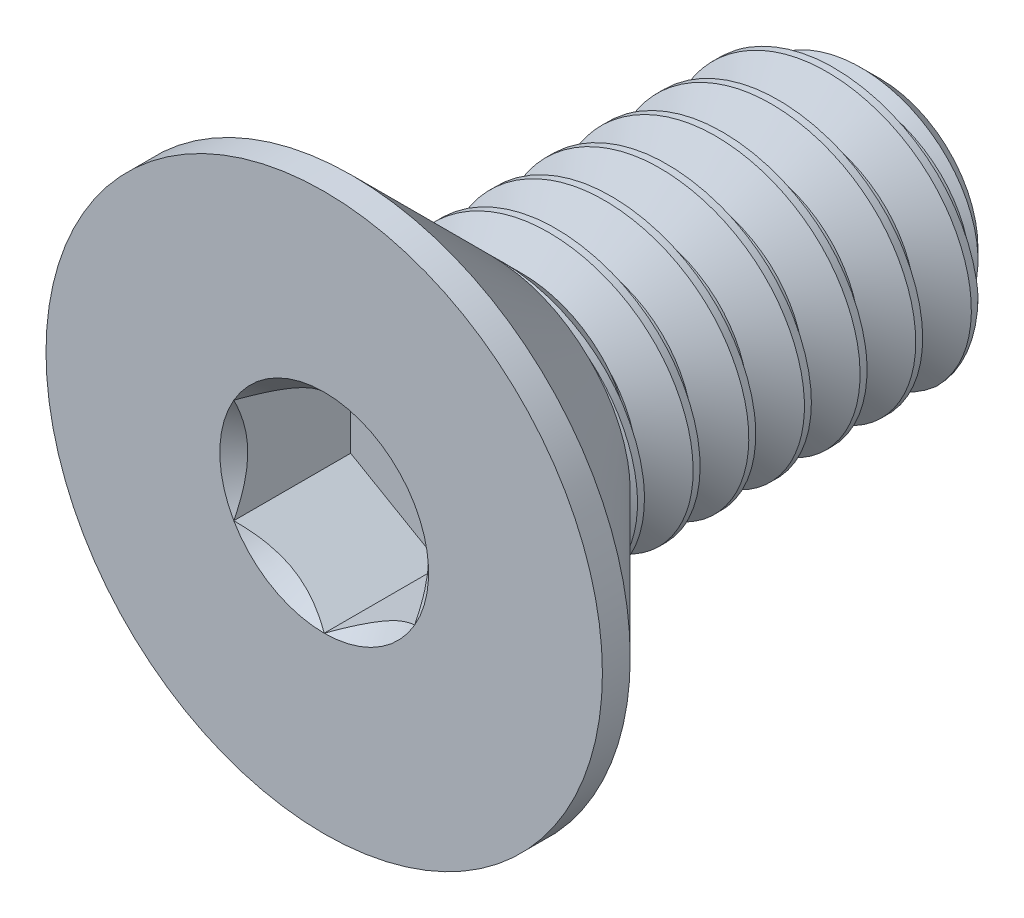
SolidWorks part; units mm, degrees
ref_plane "Front" through (0, 0, 0) normal (0, 0, 1) x (1, 0, 0)
ref_plane "Top" through (0, 0, 0) normal (0, 1, 0) x (1, 0, 0)
ref_plane "Right" through (0, 0, 0) normal (1, 0, 0) x (0, 0, -1)
sketch "Sketch1" plane through (0, 0, 0) normal (1, 0, 0) x (0, 0, -1)
  line L0 (0, 2) -> (0.2, 2) construction
  line L1 (0.2, 2) -> (1.2, 1) construction
  line L2 (0, 1) -> (4, 1)
  line L3 (4, 1) -> (4, 0)
  line L4 (4, 0) -> (0, 0)
  line L5 (0, 0) -> (0, 2) construction
  line L6 (0, 2) -> (0, -2) construction
  line L7 (4, 1) -> (4, -1) construction
  line L8 (0, -2) -> (0.2, -2) construction
  line L9 (0.2, -2) -> (1.2, -1) construction
  line L11 (0, 1) -> (0, 0)
  line L12 (1.2, 1) -> (1.2, 0) construction
  dimension "Head Ht" = 1.2
  dimension "Head Dia" = 4
  dimension "Dia" = 2
  dimension "Lg" = 4
  dimension "Head Angle" = 90
revolve "Revolve1" add sketch "Sketch1" angle 360 about L4
sketch "Sketch3" plane through (0, 0, -4) normal (0, 0, -1) x (-1, 0, 0)
  circle A0 centre (0, 0) radius 1
curve "Helix/Spiral1" pitch 0.4 height 4 radius 1 centre (0, 0, -4) axis (0, 0, 1) start towards (0, 1, 0)
sketch "Sketch2" plane through (0, 0, 0) normal (1, 0, 0) x (0, 0, -1)
  line L0 (4, 1) -> (4.35, 1)
  line L1 (4.35, 1) -> (4.2, 0.7402)
  line L2 (4.2, 0.7402) -> (4.15, 0.7402)
  line L3 (4.15, 0.7402) -> (4, 1)
  line L4 (4.075, 0.8701) -> (4.275, 0.8701) construction
  dimension "D1" = 60
  dimension "D2" = 0.05
  dimension "D3" = 0.2
chamfer "Chamfer1" distance 0.3 angle 45 1 edges at (0, 1, -4)
sweep "Cut-Sweep1" cut profiles "Sketch2" path "Helix/Spiral1"
sketch "Sketch7" plane through (0, 0, 0) normal (1, 0, 0) x (0, 0, -1)
  line L0 (0, 2) -> (0.2, 2) construction
  line L1 (0.2, 2) -> (1.2, 1) construction
  line L2 (0, 2) -> (0.2, 2)
  line L3 (0.2, 2) -> (1.2, 1)
  line L4 (1.2, 1) -> (1.2, 0) construction
  line L5 (1.2, 1) -> (1.2, 0)
  line L7 (0, 0) -> (0, 2) construction
  line L8 (0, 0) -> (0, 2)
  line L9 (0, 0) -> (1.2, 0)
  line L10 (2.2, 0) -> (-2.2, 0) construction
revolve "Revolve2" add sketch "Sketch7" angle 360 about L9
ref_plane "Plane1" through (0, 0, -1.2) normal (0, 0, 1) x (1, 0, 0)
sketch "Sketch8" plane through (0, 0, -1.2) normal (0, 0, 1) x (1, 0, 0)
  circle A0 centre (0, 0) radius 1
extrude "Boss-Extrude1" add sketch "Sketch8" against normal through all draft 45
sketch "Sketch5" plane through (0, 0, 0) normal (0, 0, 1) x (1, 0, 0)
  line L1 (0.65, -0.3753) -> (0.65, 0.3753)
  line L2 (0.65, 0.3753) -> (0, 0.7506)
  line L3 (0, 0.7506) -> (-0.65, 0.3753)
  line L4 (-0.65, 0.3753) -> (-0.65, -0.3753)
  line L5 (-0.65, -0.3753) -> (0, -0.7506)
  line L6 (0, -0.7506) -> (0.65, -0.3753)
  circle A0 centre (0, 0) radius 0.65 construction
  dimension "Hex" = 1.3
extrude "Cut-Extrude2" cut sketch "Sketch5" against normal blind 0.84
sketch "Sketch6" plane through (0, 0, 0) normal (0, 0, 1) x (1, 0, 0)
  circle A0 centre (0, 0) radius 0.7506
extrude "Cut-Extrude3" cut sketch "Sketch6" against normal blind 0.84 draft 45
sketch "Sketch9" [suppressed] plane through (0, 0, -5.5) normal (0, 0, 1) x (1, 0, 0)
  circle A1 centre (0, 0) radius 5
  circle A2 centre (0, 0) radius 5
  point P0 (0, 5)
  dimension "D1" = 0
extrude "Boss-Extrude2" [suppressed] add sketch "Sketch9" against normal offset from surface (18.5 mm away) 26 up to face at (0, 0.7, -4)
fillet "Fillet1" [suppressed] radius 0.2
sketch "Sketch10" plane through (0, 0, 0) normal (1, 0, 0) x (0, 0, -1)
  line L0 (4, 1) -> (4, -1) construction
  point P0 (3.4, -1)
  dimension "D1" = 0.6
equation "\"D3@Helix/Spiral1\" = \"Lg@Sketch1\""
equation "\"D2@Sketch2\" = \"D4@Helix/Spiral1\" * .125"
equation "\"D3@Sketch2\" = \"D4@Helix/Spiral1\" * .5"
equation "\"D1@Chamfer1\" = \"D4@Helix/Spiral1\" * .75"
equation "\"D1@Cut-Extrude2\" = \"Head Ht@Sketch1\" * .7"
equation "\"D1@Sketch10\" = \"D4@Helix/Spiral1\" * 1.5"
equation "\"D1@Cut-Extrude3\" = \"D1@Cut-Extrude2\""
equation "\"D1@Fillet1\" = \"Dia@Sketch1\" * .1"
